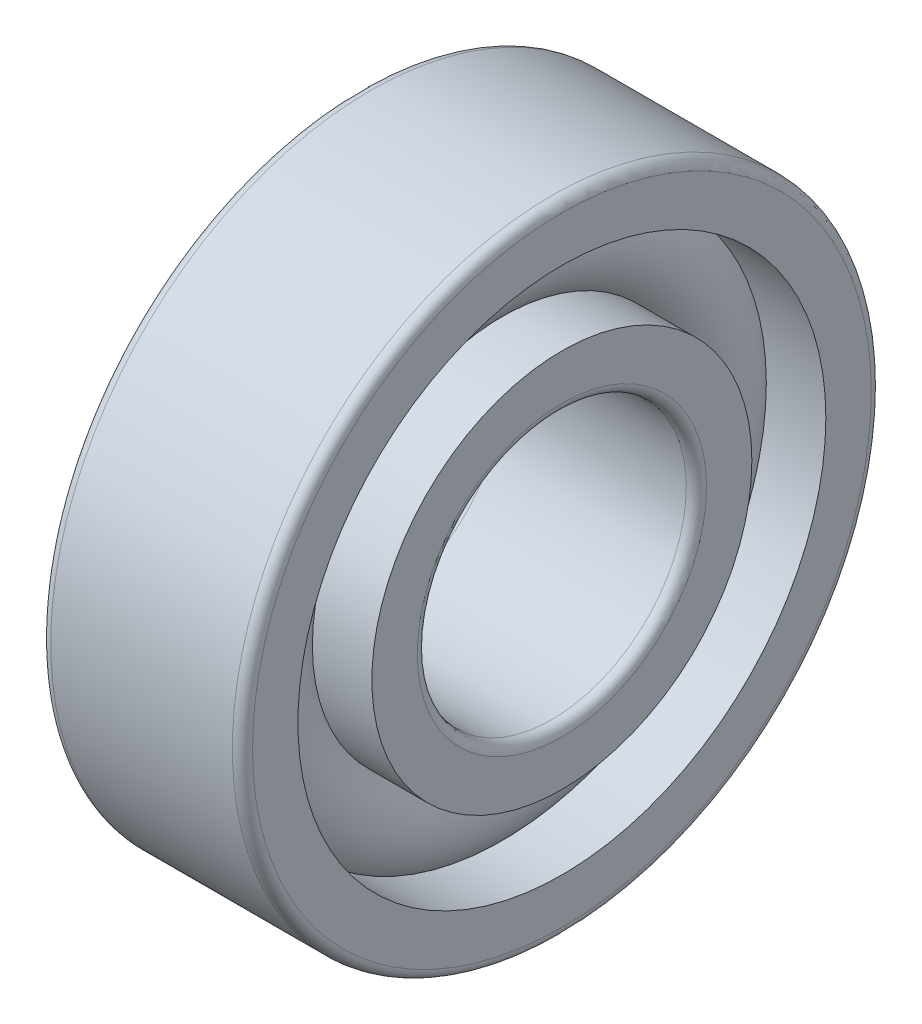
SolidWorks part; units mm, degrees
ref_plane "Plane1" through (0, 0, 0) normal (0, 0, 1) x (1, 0, 0)
ref_plane "Plane2" through (0, 0, 0) normal (0, 1, 0) x (1, 0, 0)
ref_plane "Plane3" through (0, 0, 0) normal (1, 0, 0) x (0, 0, -1)
sketch "Clipboard" plane through (0, 0, 0) normal (0, 0, 1) x (1, 0, 0)
  line L0 (-10, 0) -> (10, 0) construction
  line L1 (0, 0) -> (22.3471, -0.7804)
  line L2 (0, 0) -> (6.7459, 0.2356)
  line L3 (0, 0) -> (22.3471, -0.7804)
  line L4 (0, 0) -> (-22.3573, -0.3902)
  dimension "BallCLRad" = 6.75
sketch "CagSpiSke" plane through (0, 0, 0) normal (0, 0, 1) x (1, 0, 0)
  line L0 (0.165, 6.475) -> (0.165, 7.025)
  line L1 (0.165, 7.025) -> (-0.165, 7.025)
  line L2 (-0.165, 7.025) -> (-0.165, 6.475)
  line L3 (-0.165, 6.475) -> (0.165, 6.475)
  line L4 (-20.6375, 0) -> (20.6375, 0) construction
  line L5 (0, 0) -> (0, 23.7692) construction
  dimension "OD" = 14.05
  dimension "ID" = 12.95
revolve "CageSpine" add sketch "CagSpiSke" angle 0.001 about L4 reverse direction yes
ref_axis "Axis1" through (-50, 0, 0) along (1, 0, 0)
sketch "CagBalSke" plane through (0, 0, 0) normal (0, 0, 1) x (1, 0, 0)
  line L0 (-1.815, 6.75) -> (1.815, 6.75)
  line L1 (-1.905, 6.75) -> (1.905, 6.75) construction
  line L2 (-10, 0) -> (10, 0) construction
  line L3 (0, 0) -> (0, 24) construction
  arc A0 (1.815, 6.75) -> (-1.815, 6.75) centre (0, 6.75) cw
  dimension "BallCLRad" = 6.75
revolve "CageBall" [suppressed] add sketch "CagBalSke" angle 360 about L1 reverse direction yes
pattern_circular "CageBalls" [suppressed] count 2 every 180 about axis through (-50, 0, 0) along (1, 0, 0)
sketch "CagTrmODSke" plane through (0, 0, 0) normal (0, 0, 1) x (1, 0, 0)
  line L0 (1.816, 7.025) -> (1.816, 8.566)
  line L1 (1.816, 8.566) -> (-1.816, 8.566)
  line L2 (-1.816, 8.566) -> (-1.816, 7.025)
  line L3 (-1.816, 7.025) -> (1.816, 7.025)
  line L4 (-20.6375, 0) -> (20.6375, 0) construction
  line L5 (0, 0) -> (0, 25) construction
  dimension "Width" = 3.632
  dimension "ID" = 14.05
  dimension "OD" = 17.132
revolve "CageTrimOD" [suppressed] cut sketch "CagTrmODSke" angle 360 about L4 reverse direction yes
sketch "CagTrmIDSke" plane through (0, 0, 0) normal (0, 0, 1) x (1, 0, 0)
  line L0 (1.816, 4.936) -> (1.816, 6.475)
  line L1 (1.816, 6.475) -> (-1.816, 6.475)
  line L2 (-1.816, 6.475) -> (-1.816, 4.936)
  line L3 (-1.816, 4.936) -> (1.816, 4.936)
  line L4 (-20.6375, 0) -> (20.6375, 0) construction
  line L5 (0, 0) -> (0, 25) construction
  dimension "Width" = 3.632
  dimension "ID" = 9.872
  dimension "OD" = 12.95
revolve "CageTrimID" [suppressed] cut sketch "CagTrmIDSke" angle 360 about L4 reverse direction yes
sketch "BalSimSke" plane through (0, 0, 0) normal (0, 0, 1) x (1, 0, 0)
  line L0 (-10, 0) -> (10, 0) construction
  line L1 (-10, 6.75) -> (10, 6.75) construction
  line L2 (0, 0) -> (0, 23) construction
  circle A0 centre (0, 6.75) radius 1.65
  dimension "BallCLRad" = 6.75
  dimension "Ball_diameter" = 3.3
revolve "BallsSimplified" add sketch "BalSimSke" angle 360 about L0
sketch "BalDetSke" plane through (0, 0, 0) normal (0, 0, 1) x (1, 0, 0)
  line L0 (-1.65, 6.75) -> (1.65, 6.75)
  line L1 (-1.905, 6.75) -> (1.905, 6.75) construction
  line L2 (0, 0) -> (0, 25) construction
  arc A0 (1.65, 6.75) -> (-1.65, 6.75) centre (0, 6.75) cw
  dimension "BallCLRad" = 6.75
  dimension "Ball_diameter" = 3.3
revolve "BallDetailed" [suppressed] add sketch "BalDetSke" angle 360 about L1 reverse direction yes
sketch "InnRacSke" plane through (0, 0, 0) normal (0, 0, 1) x (1, 0, 0)
  line L0 (-1.1961, 5.65) -> (-3, 5.65)
  line L1 (-3, 5.65) -> (-3, 4.3)
  line L2 (-2.7, 4) -> (2.7, 4)
  line L3 (3, 4.3) -> (3, 5.65)
  line L4 (3, 5.65) -> (1.1961, 5.65)
  line L5 (-20.6375, 0) -> (20.6375, 0) construction
  line L6 (0, 0) -> (0, 30) construction
  arc A0 (-3, 4.3) -> (-2.7, 4) centre (-2.7, 4.3) ccw
  arc A1 (2.7, 4) -> (3, 4.3) centre (2.7, 4.3) ccw
  arc A2 (1.1961, 5.65) -> (-1.1961, 5.65) centre (0, 6.75) cw
  dimension "BallCLRad" = 6.75
  dimension "Fillet_radius" = 0.3
  dimension "Ball_diameter" = 3.25
  dimension "ID" = 8
  dimension "OD" = 11.3
  dimension "Width" = 6
revolve "InnerRace" add sketch "InnRacSke" angle 360 about L5 reverse direction yes
sketch "OutRacSke" plane through (0, 0, 0) normal (0, 0, 1) x (1, 0, 0)
  line L0 (-1.1961, 7.85) -> (-3, 7.85)
  line L1 (-3, 7.85) -> (-3, 9.2)
  line L2 (-2.7, 9.5) -> (2.7, 9.5)
  line L3 (3, 9.2) -> (3, 7.85)
  line L4 (3, 7.85) -> (1.1961, 7.85)
  line L5 (-20.6375, 0) -> (20.6375, 0) construction
  line L6 (0, 0) -> (0, 30) construction
  arc A0 (-3, 9.2) -> (-2.7, 9.5) centre (-2.7, 9.2) cw
  arc A1 (2.7, 9.5) -> (3, 9.2) centre (2.7, 9.2) cw
  arc A2 (1.1961, 7.85) -> (-1.1961, 7.85) centre (0, 6.75) ccw
  dimension "BallCLRad" = 6.75
  dimension "Fillet_radius" = 0.3
  dimension "Ball_diameter" = 3.25
  dimension "Width" = 6
revolve "OuterRace" add sketch "OutRacSke" angle 360 about L5 reverse direction yes
pattern_circular "BallsDetailed" [suppressed] count 2 every 180 about axis through (-50, 0, 0) along (1, 0, 0)
equation "\"BallCLRad@Clipboard\" = ( \"OD@OutRacSke\" + \"ID@InnRacSke\" ) / 4"
equation "\"BallCLRad@BalSimSke\" = \"BallCLRad@Clipboard\""
equation "\"BallCLRad@BalDetSke\" = \"BallCLRad@Clipboard\""
equation "\"BallCLRad@InnRacSke\" = \"BallCLRad@Clipboard\""
equation "\"BallCLRad@OutRacSke\" = \"BallCLRad@Clipboard\""
equation "\"Ball_diameter@InnRacSke\" = \"Ball_diameter@BalDetSke\" - 0.05"
equation "\"Ball_diameter@OutRacSke\" = \"Ball_diameter@BalDetSke\" - 0.05"
equation "\"Ball_diameter@BalSimSke\" = \"Ball_diameter@BalDetSke\""
equation "\"Width@OutRacSke\" = \"Width@InnRacSke\""
equation "\"Fillet_radius@OutRacSke\" = \"Fillet_radius@InnRacSke\""
equation "\"Max_count@Clipboard\" = int( 3.14159265 / atn(( \"Ball_diameter@BalDetSke\" / 2) / sqr( \"BallCLRad@Clipboard\"  *  \"BallCLRad@Clipboard\" - ( \"Ball_diameter@BalDetSke\" / 2) *  ( \"Ball_diameter@BalDetSke\" / 2))))"
equation "\"Max_count@Clipboard\" = ((sgn( \"Max_count@Clipboard\" - \"Count@Clipboard\" )-1)*( \"Max_count@Clipboard\" - \"Count@Clipboard\" ))/-2+ \"Count@Clipboard\""
equation "\"Count@BallsDetailed\" = int( \"Show_count@Clipboard\" ) "
equation "\"Count@BallsDetailed\" = ((sgn( \"Count@BallsDetailed\" - \"Max_count@Clipboard\" )-1)*( \"Count@BallsDetailed\" - \"Max_count@Clipboard\" ))/-2+ \"Max_count@Clipboard\""
equation "\"Count@BallsDetailed\" = ((sgn( \"Count@BallsDetailed\" - \"Min_count@Clipboard\" )+1)*( \"Count@BallsDetailed\" - \"Min_count@Clipboard\"))/2 +\"Min_count@Clipboard\""
equation "\"Angle@BallsDetailed\" = 360.0 / \"Max_count@Clipboard\""
equation "\"BallCLRad@CagBalSke\" = \"BallCLRad@Clipboard\""
equation "\"Count@CageBalls\" = \"Count@BallsDetailed\""
equation "\"Angle@CageBalls\" = \"Angle@BallsDetailed\""
equation "\"Angle@CageSpine\" =  \"Angle@CageBalls\" * ( \"Count@CageBalls\" -1 + int( \"Count@CageBalls\" / \"Max_count@Clipboard\" ) )  + 0.001 -  int( \"Count@CageBalls\" / \"Max_count@Clipboard\" ) * 0.001"
equation "\"Angle@CageSpine\" =  \"Angle@CageSpine\" * int( \"Min_count@Clipboard\" / 2) + int(1 / \"Min_count@Clipboard\")  * 0.001"
equation "\"CageWallOD@CagBalSke\" =  \"Ball_diameter@BalDetSke\" * 1.1"
equation "\"Thickness@CagSpiSke\" =  \"Ball_diameter@BalDetSke\" * 0.1"
equation "\"OD@CagTrmODSke\" = \"BallCLRad@Clipboard\" * 2 + \"CageWallOD@CagBalSke\" + 0.002"
equation "\"ID@CagTrmODSke\" = \"BallCLRad@Clipboard\" * 2 + \"Ball_diameter@BalDetSke\" / 6"
equation "\"OD@CagTrmIDSke\" = \"BallCLRad@Clipboard\" * 2 - \"Ball_diameter@BalDetSke\" / 6"
equation "\"ID@CagTrmIDSke\" = \"BallCLRad@Clipboard\" * 2 - \"CageWallOD@CagBalSke\" + 0.002"
equation "\"OD@CagSpiSke\" = \"ID@CagTrmODSke\""
equation "\"ID@CagSpiSke\" = \"OD@CagTrmIDSke\""
equation "\"Width@CagTrmODSke\" = \"CageWallOD@CagBalSke\" + 0.002"
equation "\"Width@CagTrmIDSke\" = \"CageWallOD@CagBalSke\" + 0.002"
